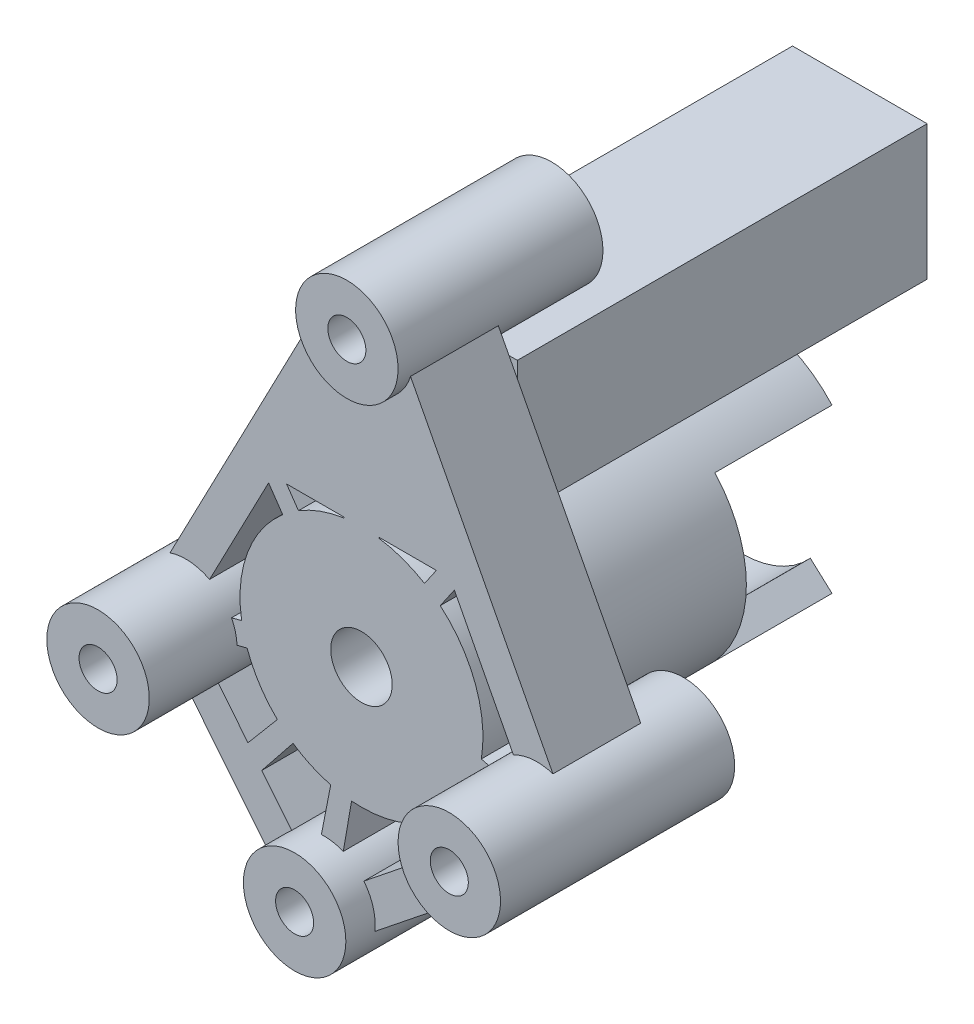
SolidWorks part; units mm, degrees
ref_plane "Front Plane" through (0, 0, 0) normal (0, 0, 1) x (1, 0, 0)
ref_plane "Top Plane" through (0, 0, 0) normal (0, 1, 0) x (1, 0, 0)
ref_plane "Right Plane" through (0, 0, 0) normal (1, 0, 0) x (0, 0, -1)
sketch "Sketch1" plane through (0, 0, 0) normal (0, 0, 1) x (1, 0, 0)
  line L1 (0, 0) -> (0, 1.5574)
  line L6 (0.5782, 10.3918) -> (0.605, 5.0022)
  line L7 (-0.605, 5.0022) -> (-0.5782, 10.3918)
  line L8 (-3.8779, -2.6243) -> (-2.4528, -0.9358)
  line L9 (-3.1735, 5.4175) -> (-2.3183, 4.1762)
  line L12 (-1.1082, 12.0782) -> (-7.1082, 0.5782)
  line L13 (1.1082, 12.0782) -> (7.1082, 0.5782)
  line L14 (-2.2561, -6.6177) -> (-6.972, -0.786)
  line L15 (-0.5029, -6.8075) -> (6.7812, -0.9758)
  line L16 (-6, 0) -> (0, 11.5)
  line L17 (-6, 0) -> (-1.2841, -5.8317)
  line L18 (6, 0) -> (-1.2841, -5.8317)
  line L19 (2.8265, 6.0825) -> (1.7823, 4.5667)
  line L20 (6, 0) -> (0, 11.5)
  line L21 (3.1735, 5.4175) -> (2.3183, 4.1762)
  line L22 (-4.7509, -0.0483) -> (-3.2708, 0.3186)
  line L23 (-3.46, 1.0467) -> (-4.94, 0.6626)
  line L25 (1.5, 7.25) -> (-1.5, 7.25)
  line L26 (2.2174, 7.25) -> (-2.2174, 7.25)
  line L27 (-0.9266, -1.8151) -> (-1.4687, -4.5954)
  line L28 (-1.5, 7.25) -> (-1.4166, 10.2488)
  line L29 (-3.4063, -3.2075) -> (-1.9305, -1.3591)
  line L30 (-0.2259, -1.9328) -> (-0.7105, -4.7211)
  line L31 (-1.4166, 10.2488) -> (0, 10.25)
  line L32 (0, 7.25) -> (0, 7.75)
  line L33 (1, 7.75) -> (-1, 7.75)
  line L34 (-1, 7.75) -> (-1, 9.75)
  line L35 (-1, 9.75) -> (1, 9.75)
  line L36 (-2.8265, 6.0825) -> (-1.7823, 4.5667)
  line L37 (2.0652, -3.1502) -> (1.3053, -1.6874)
  line L38 (2.6507, -2.6815) -> (1.9552, -1.3425)
  line L39 (1, 7.75) -> (1, 9.75)
  line L40 (1.5, 7.25) -> (1.4166, 10.2488)
  line L41 (3.46, 1.0467) -> (4.94, 0.6626)
  line L42 (4.7509, -0.0483) -> (3.2708, 0.3186)
  line L43 (1.4166, 10.2488) -> (0, 10.25)
  circle A0 centre (-6, 0) radius 0.5
  circle A1 centre (-1.2841, -5.8317) radius 0.6
  circle A2 centre (6, 0) radius 0.5
  circle A3 centre (-6, 0) radius 1.25
  circle A4 centre (6, 0) radius 1.25
  circle A5 centre (-1.2841, -5.8317) radius 1.25
  circle A6 centre (0, 11.5) radius 0.6
  circle A7 centre (0, 11.5) radius 1.25
  circle A8 centre (0, 1.5574) radius 3.1
  circle A9 centre (0, 1.5574) radius 3.4975
  circle A10 centre (0, 1.5574) radius 1.05
  point P49 (-0.9266, -3.7742)
  point P70 (0, 9.75)
extrude "Boss-Extrude7" add sketch "Sketch1" along normal blind 3 contours A8 A10 | A9 A8 | A9 L21 L20 L19 | A7 L20 A4 L13 | A7 L16 A6 L20 | L16 A7 L20 A6 | A9 L6 A7 L7 | A7 L12 A3 L16 | A9 L36 L16 L9 | A9 L23 A3 L22 | A9 L8 L17 L29 | A9 L27 A5 L30 | A9 L37 L18 L38 | A9 L42 A4 L41 | L20 A4 L18 A2 | A4 L20 A2 L18 | L17 A5 L18 A1 | L18 A5 L17 A1 | A5 L17 A3 L14 | A3 L16 A0 L17 | L16 A3 L17 A0 | A5 L15 A4 L18 region at (3.6764, 5.8815, 0) region at (0, 10.5736, 0) region at (0.4583, 10.6958, 0) region at (-3.6764, 5.8815, 0) region at (7.1815, 0.2897, 0) region at (0, 6.1403, 0) region at (-6.3651, 1.1617, 0) region at (5.2048, 0.1673, 0) region at (1.1791, 4.7449, 0) region at (2.5208, 5.0739, 0) region at (-4.1541, -3.3299, 0) region at (-5.2198, 0.0779, 0) region at (2.7643, -3.4234, 0) region at (4.0916, 0.4986, 0) region at (-2.4939, -5.7037, 0) region at (-2.5208, 5.0739, 0) region at (-4.0916, 0.4986, 0) region at (-1.1909, -4.9703, 0) region at (-2.9281, -2.0515, 0) region at (1.9925, -2.2242, 0) region at (-0.8336, -3.2697, 0) region at (-3.0123, 1.5574, 0)
extrude "Boss-Extrude8" add sketch "Sketch1<8>" along normal blind 3 contours A7 L43 L6 | L43 L20 L6 | A7 L7 L31 | L16 L31 L7 | L16 L35 L7 L31 | L6 L43 L31 L7 L35 | L34 L35 L16 L31 L28 | L35 L16 L34 L33 L7 | L35 L34 L16 | L33 L39 L20 L35 L6 | L20 L43 L6 L35 | L20 L39 L35 | L40 L43 L20 L35 L39 | L25 L40 L20 L39 L33 L6 | L35 L7 L33 L6 | L6 L33 L32 L25 | L32 L33 L7 L26 | L33 L34 L16 L28 L25 L7 | L26 L28 L16 | L40 L26 L20 region at (0.6032, 10.2969, 0) region at (0.4354, 10.2919, 0) region at (0.6954, 9.9467, 0) region at (0, 9.9997, 0) region at (1.1788, 9.7341, 0) region at (-0.4354, 10.2919, 0) region at (0.7916, 8.7457, 0) region at (0, 8.7472, 0) region at (0.971, 9.6944, 0) region at (-0.6032, 10.2969, 0) region at (-0.6954, 9.9467, 0) region at (1.1422, 8.069, 0) region at (0.2963, 7.4998, 0) region at (-0.7916, 8.7457, 0) region at (1.7257, 7.7341, 0) region at (-1.1788, 9.7341, 0) region at (-0.2963, 7.4998, 0) region at (-1.1422, 8.069, 0) region at (-0.971, 9.6944, 0) region at (-1.7257, 7.7341, 0)
sketch "Sketch1<8>" plane through (0, 0, 0) normal (0, 0, 1) x (1, 0, 0) same geometry as "Sketch1"
sketch "Sketch3" plane through (0, 0, 0) normal (0, 0, -1) x (-1, 0, 0)
  circle A0 centre (0, 11.5) radius 0.6
  circle A1 centre (0, 11.5) radius 1.25
extrude "Boss-Extrude13" add sketch "Sketch3" against normal blind 3.5 and the other way blind 3.5 separate body
sketch "Sketch4" plane through (0, 0, 0) normal (0, 0, -1) x (-1, 0, 0)
  circle A0 centre (0, 1.5574) radius 3.4975
  circle A1 centre (0, 1.5574) radius 3.05
extrude "Boss-Extrude14" add sketch "Sketch4" along normal blind 2
sketch "Sketch6" plane through (0, 0, 3) normal (0, 0, 1) x (1, 0, 0)
  circle A0 centre (-6, 0) radius 0.5
  circle A1 centre (-6, 0) radius 1.25
  circle A2 centre (6, 0) radius 1.25
  circle A3 centre (6, 0) radius 0.5
extrude "Boss-Extrude15" add sketch "Sketch6" along normal blind 3 and the other way blind 5
sketch "Sketch7" plane through (0, 0, 3) normal (0, 0, 1) x (1, 0, 0)
  circle A0 centre (-1.2841, -5.8317) radius 0.6
  circle A1 centre (-1.2841, -5.8317) radius 1.25
extrude "Boss-Extrude16" add sketch "Sketch7" along normal blind 1 and the other way blind 5
sketch "Sketch10" plane through (0, 0, 3) normal (0, 0, 1) x (1, 0, 0)
  circle A0 centre (0, 1.5574) radius 3.8394
  circle A1 centre (0, 1.5574) radius 1.05
extrude "Boss-Extrude20" add sketch "Sketch10" against normal blind 3
sketch "Sketch13" plane through (0, 0, 0) normal (0, 0, -1) x (-1, 0, 0)
  circle A0 centre (0, 11.5) radius 0.6
  circle A1 centre (0, 11.5) radius 1.26
extrude "Boss-Extrude24" add sketch "Sketch13" along normal blind 3.5 and the other way blind 3.5
sketch "Sketch14" plane through (0, 0, -2) normal (0, 0, -1) x (-1, 0, 0)
  circle A0 centre (0, 1.5574) radius 3.05
  circle A1 centre (0, 1.5574) radius 3.8394
extrude "Boss-Extrude25" add sketch "Sketch14" along normal blind 4
sketch "Sketch16" plane through (0, 0, 0) normal (0, 0, -1) x (-1, 0, 0)
  circle A0 centre (0, 1.5574) radius 3.15
extrude "Cut-Extrude1" cut sketch "Sketch16" along normal blind 10
sketch "Sketch19" plane through (0, 0, 0) normal (0, 0, -1) x (-1, 0, 0)
  line L3 (2.2732, 5.6936) -> (-2.3268, 5.6936)
  line L4 (2.2732, 5.6936) -> (2.2732, 10.2936)
  line L5 (2.2732, 10.2936) -> (-2.3268, 10.2936)
  line L6 (-2.3268, 5.6936) -> (-2.3268, 10.2936)
  line L9 (1.05, 6.9168) -> (-1.05, 6.9168)
  line L10 (1.05, 6.9168) -> (1.05, 9.0168)
  line L11 (1.05, 9.0168) -> (-1.05, 9.0168)
  line L12 (-1.05, 6.9168) -> (-1.05, 9.0168)
  point P8 (0, 7.9668)
  point P12 (0, 7.9668)
extrude "Boss-Extrude30" add sketch "Sketch19" along normal blind 14
sketch "Sketch20" plane through (0, 0, 3) normal (0, 0, 1) x (1, 0, 0)
  line L0 (-2.5587, 5.6936) -> (-2.8265, 6.0825)
  line L1 (-2.8265, 6.0825) -> (-1.9767, 4.8489) construction
  line L2 (-2.5587, 5.6936) -> (2.5587, 5.6936)
  line L3 (2.8265, 6.0825) -> (1.9767, 4.8489) construction
  line L4 (-2.8265, 6.0825) -> (-2.2174, 7.25)
  line L5 (-2.2174, 7.25) -> (-0.5938, 7.25)
  line L6 (-0.5938, 7.25) -> (-0.6016, 5.6936)
  line L7 (2.5587, 5.6936) -> (2.8265, 6.0825)
  line L8 (2.8265, 6.0825) -> (2.2174, 7.25)
  line L9 (2.2174, 7.25) -> (0.5938, 7.25)
  line L10 (0.5938, 7.25) -> (0.6016, 5.6936)
  line M1 (-0.5938, 7.25) -> (-0.6033, 5.3491)
  line M3 (-1.9767, 4.8489) -> (-2.8265, 6.0825)
  line M4 (-2.8265, 6.0825) -> (-2.2174, 7.25)
  line M5 (-2.2174, 7.25) -> (-0.5938, 7.25)
  line M44 (2.8265, 6.0825) -> (1.9767, 4.8489)
  line M46 (0.6033, 5.3491) -> (0.5938, 7.25)
  line M47 (0.5938, 7.25) -> (2.2174, 7.25)
  line M48 (2.2174, 7.25) -> (2.8265, 6.0825)
extrude "Boss-Extrude31" add sketch "Sketch20" against normal blind 3 contours L2 M3 M1 M5 M4 | L2 M46 M44 M48 M47 region at (1.5888, 6.4382, 3) region at (-1.5888, 6.4382, 3)
sketch "Sketch21" plane through (0, 0, 0) normal (0, 0, -1) x (-1, 0, 0)
  circle A0 centre (0, 1.5574) radius 4.15
  circle A1 centre (0, 1.5574) radius 3.7
extrude "Boss-Extrude32" add sketch "Sketch21" along normal blind 6 and the other way blind 3
sketch "Sketch23" plane through (0, 0, -3.5) normal (0, 0, -1) x (-1, 0, 0)
  circle A0 centre (0, 11.5) radius 0.65
  circle A1 centre (-6, 0) radius 0.65
  circle A2 centre (1.2841, -5.8317) radius 0.65
  circle A3 centre (6, 0) radius 0.65
  circle A4 centre (0, 11.5) radius 0.6
  circle A5 centre (-6, 0) radius 0.5
  circle A6 centre (1.2841, -5.8317) radius 0.6
  circle A7 centre (6, 0) radius 0.5
extrude "Cut-Extrude3" cut sketch "Sketch23" against normal through all
sketch "Sketch24" plane through (0, 0, -2) normal (0, 0, -1) x (-1, 0, 0)
  circle A0 centre (-6, 0) radius 1.75
  circle A1 centre (0, 11.5) radius 1.75
  circle A2 centre (6, 0) radius 1.75
  circle A3 centre (1.2841, -5.8317) radius 1.75
  circle A4 centre (0, 11.5) radius 1.26
  circle A5 centre (-6, 0) radius 1.25
  circle A6 centre (1.2841, -5.8317) radius 1.25
  circle A7 centre (6, 0) radius 1.25
extrude "Boss-Extrude34" add sketch "Sketch24" against normal blind 8
sketch "Sketch25" plane through (0, 0, -3.5) normal (0, 0, -1) x (-1, 0, 0)
  circle A1 centre (0, 11.5) radius 1.26
  circle A2 centre (0, 11.5) radius 1.75
extrude "Boss-Extrude35" add sketch "Sketch25" against normal blind 2
sketch "Sketch28" plane through (0, 0, 6) normal (0, 0, 1) x (1, 0, 0)
  circle A0 centre (0, 11.5) radius 1.26
  circle A1 centre (0, 11.5) radius 1.75
extrude "Cut-Extrude4" cut sketch "Sketch28" against normal blind 2.5
sketch "Sketch29" plane through (0, 0, 4) normal (0, 0, 1) x (1, 0, 0)
  circle A0 centre (-1.2841, -5.8317) radius 1.25
  circle A1 centre (-1.2841, -5.8317) radius 1.75
extrude "Cut-Extrude5" cut sketch "Sketch29" along normal blind 5.5
sketch "Sketch30" plane through (0, 0, -6) normal (0, 0, -1) x (-1, 0, 0)
  line L1 (-3.076, 4.3433) -> (-2.3348, 3.672)
  line L4 (3.076, 4.3433) -> (2.3348, 3.672)
  line L5 (3.076, -1.2284) -> (2.3348, -0.5571)
  line L6 (-3.076, -1.2284) -> (-2.3348, -0.5571)
  arc A0 (-0.3379, 5.6936) -> (0.3379, 5.6936) centre (0, 1.5574) ccw construction
  circle A1 centre (0, 1.5574) radius 3.15 construction
  arc A2 (-2.3348, 3.672) -> (2.3432, 3.6627) centre (0, 1.5574) cw
  arc A3 (-3.076, 4.3433) -> (3.076, 4.3433) centre (0, 1.5574) cw
  arc A4 (-2.3348, -0.5571) -> (2.3432, -0.5478) centre (0, 1.5574) ccw
  arc A5 (-3.076, -1.2284) -> (3.076, -1.2284) centre (0, 1.5574) ccw
  line M5 (0.3379, 5.6936) -> (-0.3379, 5.6936)
  arc M6 (-0.3379, 5.6936) -> (0.3379, 5.6936) centre (0, 1.5574) ccw
  circle M7 centre (0, 1.5574) radius 3.15
extrude "Boss-Extrude36" add sketch "Sketch30" along normal blind 4 contours L4 L1 M6 M5 M7 | L6 L5 M6 M7 region at (0, 4.8173, -6) region at (0, -1.7034, -6)
